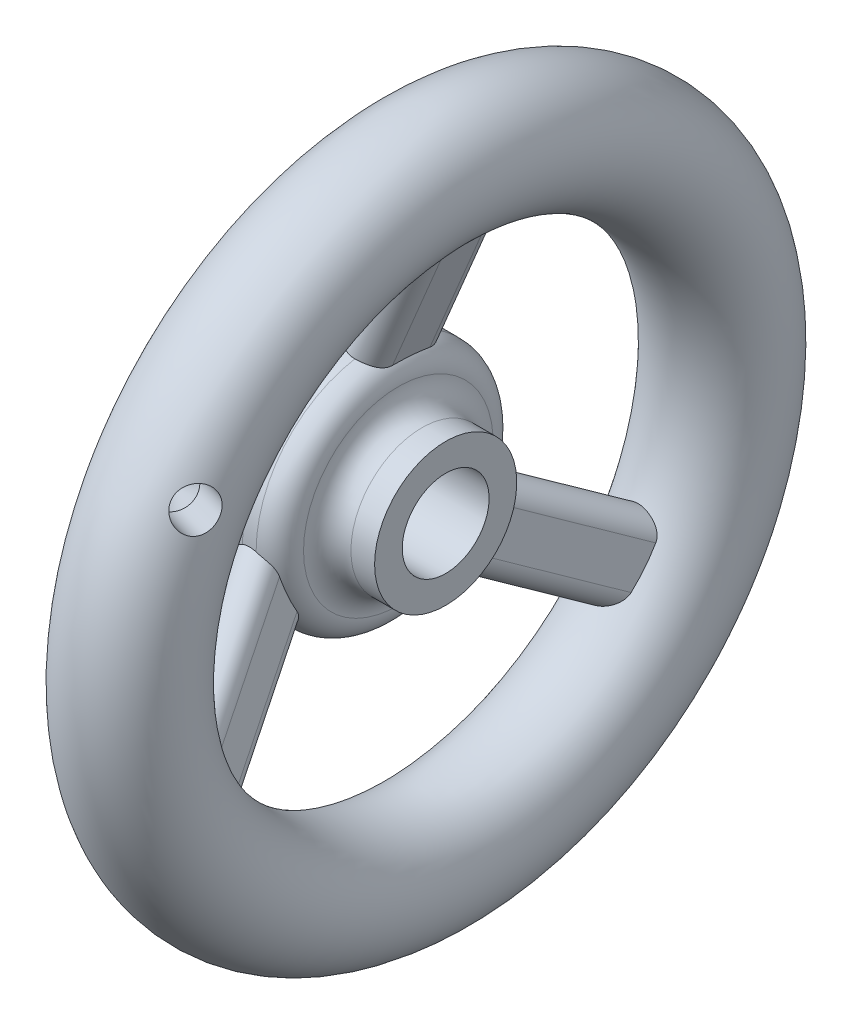
SolidWorks part; units mm, degrees
ref_plane "Front Plane" through (0, 0, 0) normal (0, 0, 1) x (1, 0, 0)
ref_plane "Top Plane" through (0, 0, 0) normal (0, 1, 0) x (1, 0, 0)
ref_plane "Right Plane" through (0, 0, 0) normal (1, 0, 0) x (0, 0, -1)
sketch "Sketch1" plane through (0, 0, 0) normal (0, 0, 1) x (1, 0, 0)
  line L0 (0, 0) -> (26.2789, 0) construction
  line L1 (0, 5.5) -> (24, 5.5)
  line L2 (24, 5.5) -> (24, 9)
  line L3 (24, 9) -> (21, 9)
  line L5 (0, 5.5) -> (0, 11)
  line L7 (13.2665, 15) -> (15, 15)
  arc A5 (0, 11) -> (13.2665, 15) centre (13.2665, -9) cw
  arc A6 (21, 9) -> (18, 12) centre (21, 12) cw
  arc A8 (18, 12) -> (15, 15) centre (15, 12) ccw
  dimension "D4" = 15
  dimension "D7" = 24
  dimension "D8" = 3
  dimension "D9" = 24
  dimension "D5" = 3
  dimension "D1" = 5.5
  dimension "D2" = 9
  dimension "D3" = 3
  dimension "D6" = 11
revolve "Revolve1" add sketch "Sketch1" angle 360 about L0
sketch "Sketch2" plane through (0, 0, 0) normal (0, 0, 1) x (1, 0, 0)
  line L0 (29, 37.5) -> (29, 23.5324) construction
  line L1 (24, -9) -> (24, 9) construction
  line L2 (0, 0) -> (28.2848, 0) construction
  circle A0 centre (21.5, 37.5) radius 7.5
  dimension "D1" = 15
  dimension "D2" = 5
  dimension "D3" = 37.5
revolve "Revolve2" add sketch "Sketch2" angle 360 about L2
sketch "Sketch3" plane through (0, 0, 0) normal (0, 0, 1) x (1, 0, 0)
  line L0 (26.683, 42.9209) -> (15, 15)
  arc A0 (29, 37.5) -> (14, 37.5) centre (21.5, 37.5) ccw construction
ref_plane "Plane1" through (15, 15, 0) normal (-0.386, -0.9225, 0) x (-0.9225, 0.386, 0)
sketch "Sketch4" plane through (15, 15, 0) normal (-0.386, -0.9225, 0) x (-0.9225, 0.386, 0)
  line L0 (0.0049, 0) -> (0.0049, 5) construction
  line L1 (-2.4951, 0) -> (-2.4951, 5)
  line L2 (2.5049, 0) -> (2.5049, 5)
  arc A0 (-2.4951, 0) -> (2.5049, 0) centre (0.0049, 0) ccw
  arc A1 (2.5049, 5) -> (-2.4951, 5) centre (0.0049, 5) ccw
  point P2 (0.0049, 2.5)
  dimension "D2" = 2.5
  dimension "D1" = 5
extrude "Boss-Extrude1" add sketch "Sketch4" along normal up to next and the other way up to next contours L2 A1 L1 A0
pattern_circular "CirPattern1" count 3 over 360 about axis through (0, 0, 0) along (1, 0, 0) of "Boss-Extrude1"
sketch "Sketch5" plane through (0, 0, 0) normal (0, 1, 0) x (1, 0, 0)
  line L0 (24, -9) -> (24, 9) construction
  circle A0 centre (4, 0) radius 2
  dimension "D1" = 4
  dimension "D2" = 20
extrude "Cut-Extrude1" cut sketch "Sketch5" against normal mid plane 40
hole_wizard "M6x1.0 Tapped Hole1" positions "3DSketch1" profile "Sketch6" tap size "M6x1.0" standard "ANSI Metric"
sketch3d "3DSketch1"
  point P0 (27.9569, 21.1693, 35.4801)
sketch "Sketch6" plane through (27.9569, 21.1693, 35.4801) normal (-0.4971, 0.6135, 0.6135) x (0.1081, 0.7454, -0.6578)
  line L0 (0, 0) -> (0, 8.5022)
  line L1 (0, 8.5022) -> (2.5, 7)
  line L2 (2.5, 7) -> (2.5, 0)
  line L5 (2.5, 0) -> (0, 0)
  line L10 (0, 8.5022) -> (-2.5, 7) construction
  line L11 (0, -6.35) -> (0, 107.95) construction
  dimension "Tap Drill Dia." = 5
  dimension "Tap Drill Depth" = 7
  dimension "Drill Angle" = 118
cosmetic thread "Hole Thread1" parameters "D1"=6, "D2"=6
